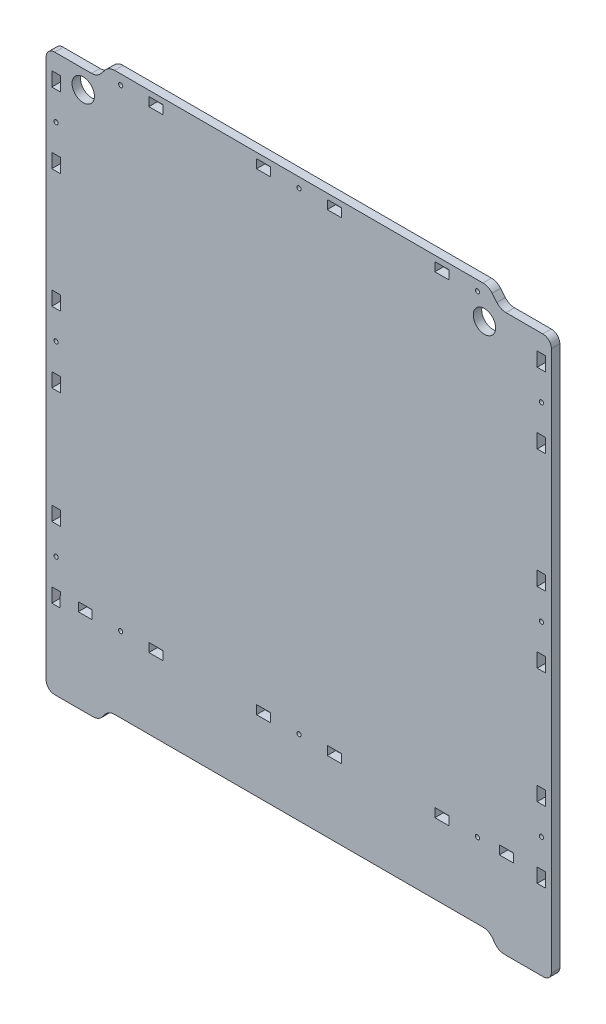
SolidWorks part; units mm, degrees
ref_plane "Спереди" through (0, 0, 0) normal (0, 0, 1) x (1, 0, 0)
ref_plane "Сверху" through (0, 0, 0) normal (0, 1, 0) x (1, 0, 0)
ref_plane "Справа" through (0, 0, 0) normal (1, 0, 0) x (0, 0, -1)
sketch "Эскиз1" plane through (0, 0, 0) normal (0, 0, 1) x (1, 0, 0)
  line L0 (146.8614, 191.5323) -> (172.8978, 191.5323)
  line L1 (-168.1022, 44.9723) -> (-168.1022, 34.9723)
  line L2 (174.8978, 34.9723) -> (168.8978, 34.9723)
  line L3 (178.8978, 185.543) -> (178.8978, -196.6758)
  line L4 (-178.1022, 185.543) -> (-178.1022, -195.7677)
  line L5 (172.8978, -201.7677) -> (145.8614, -201.7677)
  line L6 (-138.5545, -198.7314) -> (-136.2586, -195.7117)
  line L7 (-172.1022, -201.7677) -> (-145.0658, -201.7677)
  line L8 (-129.7473, -192.6754) -> (130.5428, -192.6754)
  line L9 (139.35, -198.7314) -> (137.0542, -195.7117)
  line L10 (174.8978, 179.1323) -> (174.8978, 169.359)
  line L11 (96.6207, 197.6263) -> (106.4199, 197.6434)
  line L12 (106.4199, 197.6434) -> (106.6207, 197.6263)
  line L13 (174.8978, 169.359) -> (174.8978, 169.1323)
  line L14 (137.0542, 198.496) -> (140.35, 194.5682)
  line L15 (130.5428, 201.5323) -> (-129.7473, 201.5323)
  line L16 (-136.2586, 198.4964) -> (-139.5545, 194.5686)
  line L17 (-146.0658, 191.5323) -> (-172.1022, 191.5323)
  line L18 (106.4199, 191.4434) -> (96.6207, 191.4265)
  line L19 (-168.1022, 34.9723) -> (-174.1022, 34.9723)
  line L20 (30.5209, -142.6754) -> (20.5466, -142.6754)
  line L21 (168.8978, 34.9723) -> (168.8978, 44.9723)
  line L22 (30.5209, -136.4756) -> (30.5209, -142.6754)
  line L23 (-29.4488, -136.4756) -> (-19.4791, -136.4756)
  line L24 (20.5466, -142.6754) -> (20.5466, -136.4756)
  line L25 (-19.4791, -142.6754) -> (-29.4488, -142.6754)
  line L26 (-19.4791, -136.4756) -> (-19.4791, -142.6754)
  line L27 (-168.1022, 179.1323) -> (-168.1022, 169.1323)
  line L28 (-29.4488, -142.6754) -> (-29.4488, -136.4756)
  line L29 (-174.1022, 34.9723) -> (-174.1022, 44.9723)
  line L30 (-174.1022, 44.9723) -> (-168.1022, 44.9723)
  line L31 (20.5466, -136.4756) -> (30.5209, -136.4756)
  line L32 (-174.1022, 179.1323) -> (-168.1022, 179.1323)
  line L33 (106.6155, -142.6768) -> (96.6207, -142.6768)
  line L34 (96.6207, -142.6768) -> (96.6207, -136.477)
  line L35 (96.6207, -136.477) -> (106.6155, -136.477)
  line L36 (106.6155, -136.477) -> (106.6155, -142.6768)
  line L37 (152.0021, -142.6768) -> (142.1529, -142.6768)
  line L38 (142.1529, -142.6768) -> (142.1529, -136.477)
  line L39 (142.1529, -136.477) -> (152.0021, -136.477)
  line L40 (152.0021, -136.477) -> (152.0021, -142.6768)
  line L41 (-19.477, 191.4289) -> (-29.4488, 191.4289)
  line L42 (-29.4488, 191.4289) -> (-29.4488, 197.6287)
  line L43 (-29.4488, 197.6287) -> (-19.477, 197.6287)
  line L44 (-19.477, 197.6287) -> (-19.477, 191.4289)
  line L45 (-174.1022, 119.1323) -> (-174.1022, 129.1323)
  line L46 (-145.5736, -136.477) -> (-145.5736, -142.6768)
  line L47 (-155.4227, -136.477) -> (-145.5736, -136.477)
  line L48 (20.5466, 197.6287) -> (30.523, 197.6287)
  line L49 (30.523, 197.6287) -> (30.523, 191.4289)
  line L50 (-145.5736, -142.6768) -> (-155.4227, -142.6768)
  line L51 (-174.1022, -5.0277) -> (-168.1022, -5.0277)
  line L52 (-174.1022, -15.0277) -> (-174.1022, -5.0277)
  line L53 (-174.1022, 169.1323) -> (-174.1022, 179.1323)
  line L54 (-168.1022, -5.0277) -> (-168.1022, -15.0277)
  line L55 (30.523, 191.4289) -> (20.5466, 191.4289)
  line L56 (-155.4227, -142.6768) -> (-155.4227, -136.477)
  line L57 (-168.1022, 119.1323) -> (-174.1022, 119.1323)
  line L58 (-168.1022, -15.0277) -> (-174.1022, -15.0277)
  line L59 (20.5466, 191.4289) -> (20.5466, 197.6287)
  line L60 (-168.1022, 169.1323) -> (-174.1022, 169.1323)
  line L61 (-174.1022, -86.7577) -> (-168.1022, -86.7577)
  line L62 (-174.1022, -96.7577) -> (-174.1022, -86.7577)
  line L63 (-168.1022, 129.1323) -> (-168.1022, 119.1323)
  line L64 (-174.1022, 129.1323) -> (-168.1022, 129.1323)
  line L65 (-174.1022, -136.7477) -> (-168.1022, -136.7477)
  line L66 (-174.1022, -146.7477) -> (-174.1022, -136.7477)
  line L67 (-105.5235, -142.6768) -> (-105.5235, -136.477)
  line L68 (-105.5235, -136.477) -> (-95.5735, -136.477)
  line L69 (-95.5735, -136.477) -> (-95.5735, -142.6768)
  line L70 (-168.2894, -146.7477) -> (-174.1022, -146.7477)
  line L71 (-168.1022, -136.7477) -> (-168.2894, -146.7477)
  line L72 (-168.1022, -96.7577) -> (-174.1022, -96.7577)
  line L73 (-168.1022, -86.7577) -> (-168.1022, -96.7577)
  line L74 (174.8978, -15.0277) -> (168.8978, -15.0277)
  line L75 (168.8978, -96.7577) -> (168.8978, -86.7577)
  line L76 (174.8978, -5.0277) -> (174.8978, -15.0277)
  line L77 (174.8978, -86.7577) -> (174.8978, -96.7577)
  line L78 (174.8978, -96.7577) -> (168.8978, -96.7577)
  line L79 (168.8978, -146.7477) -> (168.8978, -136.7477)
  line L80 (168.8978, -136.7477) -> (174.8978, -136.7477)
  line L81 (174.8978, -136.7477) -> (174.8978, -146.7477)
  line L82 (168.8978, -86.7577) -> (174.8978, -86.7577)
  line L83 (168.8978, 179.1323) -> (174.8978, 179.1323)
  line L84 (168.8978, 119.1323) -> (168.8978, 129.1323)
  line L85 (168.8978, 129.1323) -> (174.8978, 129.1323)
  line L86 (174.8978, 129.1323) -> (174.8978, 119.1323)
  line L87 (168.8978, 44.9723) -> (174.8978, 44.9723)
  line L88 (174.8978, 169.1323) -> (168.8978, 169.1323)
  line L89 (174.8978, 44.9723) -> (174.8978, 34.9723)
  line L90 (-95.5504, 191.4265) -> (-105.5235, 191.4265)
  line L91 (106.6207, 191.4265) -> (106.4199, 191.4434)
  line L92 (-105.5235, 191.4265) -> (-105.5235, 197.6263)
  line L93 (174.8978, 119.1323) -> (168.8978, 119.1323)
  line L94 (-105.5235, 197.6263) -> (-95.5504, 197.6263)
  line L95 (-95.5504, 197.6263) -> (-95.5504, 191.4265)
  line L96 (174.8978, -146.7477) -> (168.8978, -146.7477)
  line L97 (168.8978, 169.1323) -> (168.8978, 179.1323)
  line L98 (106.6207, 197.6263) -> (106.6207, 191.4265)
  line L99 (-95.5735, -142.6768) -> (-105.5235, -142.6768)
  line L100 (96.6207, 191.4265) -> (96.6207, 197.6263)
  line L101 (168.8978, -15.0277) -> (168.8978, -5.0277)
  line L102 (168.8978, -5.0277) -> (174.8978, -5.0277)
  arc A0 (-172.1022, 191.5323) -> (-178.1022, 185.543) centre (-172.1022, 185.5323) ccw
  circle A1 centre (126.6857, -139.5423) radius 1.5
  circle A2 centre (0.6186, -139.5423) radius 1.5
  circle A3 centre (-125.5067, -139.5423) radius 1.5
  arc A4 (172.8978, -201.7677) -> (178.8978, -196.6758) centre (173.3519, -196.2218) ccw
  arc A5 (-129.7473, -192.6754) -> (-136.2586, -195.7117) centre (-129.7473, -201.1754) ccw
  arc A6 (139.35, -198.7314) -> (145.8614, -201.7677) centre (145.8614, -193.2677) ccw
  arc A7 (-145.0658, -201.7677) -> (-138.5545, -198.7314) centre (-145.0658, -193.2677) ccw
  arc A8 (-178.1022, -195.7677) -> (-172.1022, -201.7677) centre (-172.1022, -195.7677) ccw
  arc A9 (137.0542, -195.7117) -> (130.5428, -192.6754) centre (130.5428, -201.1754) ccw
  arc A10 (178.8978, 185.543) -> (172.8978, 191.5323) centre (172.8978, 185.5323) ccw
  arc A11 (137.0542, 198.496) -> (130.5428, 201.5323) centre (130.5428, 193.0323) ccw
  arc A12 (140.35, 194.5682) -> (146.8614, 191.5323) centre (146.861, 200.0323) ccw
  circle A13 centre (-171.1022, -116.7377) radius 1.5
  circle A14 centre (-171.1022, 14.9723) radius 1.5
  circle A15 centre (171.8978, 149.1323) radius 1.5
  circle A16 centre (126.705, 194.5806) radius 1.5
  circle A17 centre (-151.9022, 178.5323) radius 7.9
  circle A18 centre (171.8978, -116.7377) radius 1.5
  circle A19 centre (171.8978, 14.9723) radius 1.5
  circle A20 centre (-171.1022, 149.1323) radius 1.5
  circle A21 centre (-125.4678, 194.5806) radius 1.5
  circle A22 centre (0.6009, 194.5806) radius 1.5
  circle A23 centre (131.5978, 178.5323) radius 7.9
  arc A24 (-129.7473, 201.5323) -> (-136.2586, 198.4964) centre (-129.7476, 193.0323) ccw
  arc A25 (-146.0658, 191.5323) -> (-139.5545, 194.5686) centre (-146.0658, 200.0323) ccw
  point P155 (-174.1022, 124.1323)
  point P156 (-171.1958, -146.7477)
  dimension "D1" = 357
  dimension "D2" = 403.3
  dimension "D3" = 403.3
  dimension "D4" = 23
  dimension "D5" = 26.2
  dimension "D6" = 4
  dimension "D7" = 10
  dimension "D8" = 22.4
  dimension "D9" = 10
  dimension "D10" = 7
  dimension "D11" = 20
  dimension "D12" = 20
  dimension "D13" = 10
  dimension "D14" = 74.16
  dimension "D15" = 4
  dimension "D16" = 6
  dimension "D17" = 6
  dimension "D18" = 10
  dimension "D19" = 4
  dimension "D20" = 20
  dimension "D21" = 20
  dimension "D22" = 10
  dimension "D23" = 7
  dimension "D24" = 4
  dimension "D25" = 71.73
  dimension "D26" = 4
  dimension "D27" = 10
  dimension "D28" = 19.98
  dimension "D29" = 7
  dimension "D30" = 20.01
  dimension "D31" = 10
  dimension "D32" = 55.02
  dimension "D33" = 4
  dimension "D34" = 23
  dimension "D35" = 47.3
  dimension "D36" = 10
  dimension "D37" = 12.4
  dimension "D38" = 10
  dimension "D39" = 20
  dimension "D40" = 20
  dimension "D41" = 10
  dimension "D42" = 74.16
  dimension "D43" = 10
  dimension "D44" = 6
  dimension "D45" = 6
  dimension "D46" = 6
  dimension "D47" = 6
  dimension "D48" = 6
  dimension "D49" = 4
  dimension "D50" = 7
  dimension "D51" = 4
  dimension "D52" = 6
  dimension "D53" = 6
  dimension "D54" = 4
  dimension "D55" = 20
  dimension "D56" = 20
  dimension "D57" = 7
  dimension "D58" = 4
  dimension "D59" = 6
  dimension "D60" = 71.73
  dimension "D61" = 4
  dimension "D62" = 6
  dimension "D63" = 7
  dimension "D64" = 19.98
  dimension "D65" = 20.01
  dimension "D66" = 10
  dimension "D67" = 6
  dimension "D68" = 4
  dimension "D69" = 55.02
extrude "Бобышка-Вытянуть1" add sketch "Эскиз1" along normal blind 6
